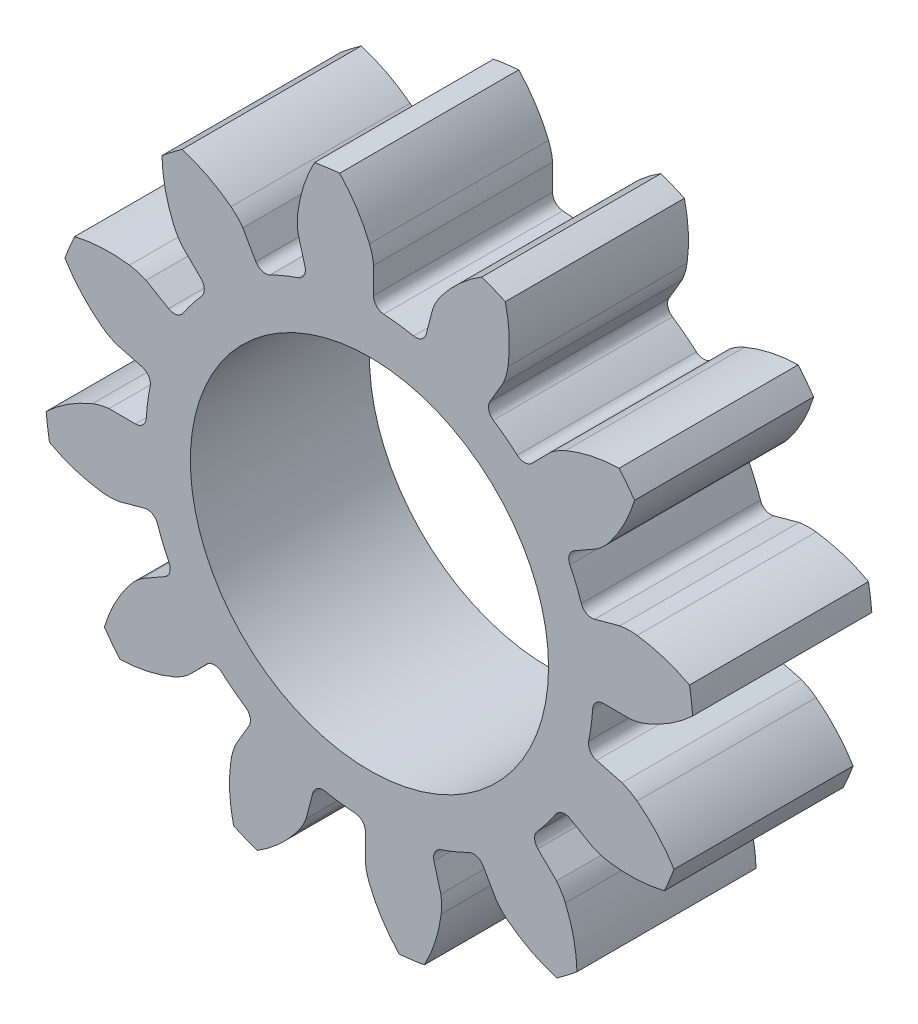
SolidWorks part; units mm, degrees
ref_plane "Front Plane" through (0, 0, 0) normal (0, 0, 1) x (1, 0, 0)
ref_plane "Top Plane" through (0, 0, 0) normal (0, 1, 0) x (1, 0, 0)
ref_plane "Right Plane" through (0, 0, 0) normal (1, 0, 0) x (0, 0, -1)
sketch "Sketch1" plane through (0, 0, 0) normal (0, 0, 1) x (1, 0, 0)
  line L48 (-0.7974, 2.7963) -> (-0.7199, 2.5139)
  line L49 (-1.2685, 2.2867) -> (-1.4135, 2.5411)
  line L50 (-2.0887, 2.023) -> (-1.8804, 1.8171)
  line L51 (-2.2419, 1.346) -> (-2.4946, 1.4939)
  line L52 (-2.8204, 0.7076) -> (-2.5371, 0.6335)
  line L53 (-2.6146, 0.0448) -> (-2.9074, 0.0465)
  line L54 (-2.7963, -0.7974) -> (-2.5139, -0.7199)
  line L55 (-2.2867, -1.2685) -> (-2.5411, -1.4135)
  line L56 (-2.023, -2.0887) -> (-1.8171, -1.8804)
  line L57 (-1.346, -2.2419) -> (-1.4939, -2.4946)
  line L58 (-0.7076, -2.8204) -> (-0.6335, -2.5371)
  line L59 (-0.0448, -2.6146) -> (-0.0465, -2.9074)
  line L60 (0.7974, -2.7963) -> (0.7199, -2.5139)
  line L61 (1.2685, -2.2867) -> (1.4135, -2.5411)
  line L62 (2.0887, -2.023) -> (1.8804, -1.8171)
  line L63 (2.2419, -1.346) -> (2.4946, -1.4939)
  line L64 (2.8204, -0.7076) -> (2.5371, -0.6335)
  line L65 (2.6146, -0.0448) -> (2.9074, -0.0465)
  line L66 (2.7963, 0.7974) -> (2.5139, 0.7199)
  line L67 (2.2867, 1.2685) -> (2.5411, 1.4135)
  line L68 (2.023, 2.0887) -> (1.8171, 1.8804)
  line L69 (1.346, 2.2419) -> (1.4939, 2.4946)
  line L70 (0.7076, 2.8204) -> (0.6335, 2.5371)
  line L71 (0.0448, 2.6146) -> (0.0465, 2.9074)
  circle A0 centre (0, 0) radius 2
  arc A192 (0.0001, 3.0941) -> (-0.3326, 3.6101) centre (-1.5335, 2.4705) ccw
  arc A193 (-0.3326, 3.6101) -> (-0.6131, 3.5732) centre (0, 0) ccw
  arc A194 (-0.6131, 3.5732) -> (-0.8009, 2.9887) centre (0.8418, 2.7833) ccw
  arc A195 (-0.8009, 2.9887) -> (-0.7974, 2.7963) centre (-0.1305, 2.9048) ccw
  arc A196 (-0.7982, 2.3667) -> (-0.7199, 2.5139) centre (-0.8371, 2.4818) ccw
  arc A197 (-0.7982, 2.3667) -> (-1.1091, 2.2379) centre (0, 0) ccw
  arc A198 (-1.2685, 2.2867) -> (-1.1091, 2.2379) centre (-1.163, 2.3468) ccw
  arc A199 (-1.4135, 2.5411) -> (-1.547, 2.6796) centre (-1.9617, 2.1463) ccw
  arc A200 (-1.547, 2.6796) -> (-2.0931, 2.9601) centre (-2.5633, 1.3728) ccw
  arc A201 (-2.0931, 2.9601) -> (-2.3175, 2.7879) centre (0, 0) ccw
  arc A202 (-2.3175, 2.7879) -> (-2.1879, 2.1878) centre (-0.6626, 2.8313) ccw
  arc A203 (-2.1879, 2.1878) -> (-2.0887, 2.023) centre (-1.5655, 2.4504) ccw
  arc A204 (-1.8746, 1.6505) -> (-1.8804, 1.8171) centre (-1.9658, 1.7307) ccw
  arc A205 (-1.8746, 1.6505) -> (-2.0794, 1.3836) centre (0, 0) ccw
  arc A206 (-2.2419, 1.346) -> (-2.0794, 1.3836) centre (-2.1806, 1.4509) ccw
  arc A207 (-2.4946, 1.4939) -> (-2.6795, 1.5472) centre (-2.7721, 0.8779) ccw
  arc A208 (-2.6795, 1.5472) -> (-3.2927, 1.517) centre (-2.9063, -0.0927) ccw
  arc A209 (-3.2927, 1.517) -> (-3.401, 1.2556) centre (0, 0) ccw
  arc A210 (-3.401, 1.2556) -> (-2.9887, 0.8007) centre (-1.9895, 2.1206) ccw
  arc A211 (-2.9887, 0.8007) -> (-2.8204, 0.7076) centre (-2.5809, 1.3394) ccw
  arc A212 (-2.4487, 0.492) -> (-2.5371, 0.6335) centre (-2.5678, 0.516) ccw
  arc A213 (-2.4487, 0.492) -> (-2.4926, 0.1585) centre (0, 0) ccw
  arc A214 (-2.6146, 0.0448) -> (-2.4926, 0.1585) centre (-2.6139, 0.1662) ccw
  arc A215 (-2.9074, 0.0465) -> (-3.0941, 0.0001) centre (-2.8396, -0.6257) ccw
  arc A216 (-3.0941, 0.0001) -> (-3.6101, -0.3326) centre (-2.4705, -1.5335) ccw
  arc A217 (-3.6101, -0.3326) -> (-3.5732, -0.6131) centre (0, 0) ccw
  arc A218 (-3.5732, -0.6131) -> (-2.9887, -0.8009) centre (-2.7833, 0.8418) ccw
  arc A219 (-2.9887, -0.8009) -> (-2.7963, -0.7974) centre (-2.9048, -0.1305) ccw
  arc A220 (-2.3667, -0.7982) -> (-2.5139, -0.7199) centre (-2.4818, -0.8371) ccw
  arc A221 (-2.3667, -0.7982) -> (-2.2379, -1.1091) centre (0, 0) ccw
  arc A222 (-2.2867, -1.2685) -> (-2.2379, -1.1091) centre (-2.3468, -1.163) ccw
  arc A223 (-2.5411, -1.4135) -> (-2.6796, -1.547) centre (-2.1463, -1.9617) ccw
  arc A224 (-2.6796, -1.547) -> (-2.9601, -2.0931) centre (-1.3728, -2.5633) ccw
  arc A225 (-2.9601, -2.0931) -> (-2.7879, -2.3175) centre (0, 0) ccw
  arc A226 (-2.7879, -2.3175) -> (-2.1878, -2.1879) centre (-2.8313, -0.6626) ccw
  arc A227 (-2.1878, -2.1879) -> (-2.023, -2.0887) centre (-2.4504, -1.5655) ccw
  arc A228 (-1.6505, -1.8746) -> (-1.8171, -1.8804) centre (-1.7307, -1.9658) ccw
  arc A229 (-1.6505, -1.8746) -> (-1.3836, -2.0794) centre (0, 0) ccw
  arc A230 (-1.346, -2.2419) -> (-1.3836, -2.0794) centre (-1.4509, -2.1806) ccw
  arc A231 (-1.4939, -2.4946) -> (-1.5472, -2.6795) centre (-0.8779, -2.7721) ccw
  arc A232 (-1.5472, -2.6795) -> (-1.517, -3.2927) centre (0.0927, -2.9063) ccw
  arc A233 (-1.517, -3.2927) -> (-1.2556, -3.401) centre (0, 0) ccw
  arc A234 (-1.2556, -3.401) -> (-0.8007, -2.9887) centre (-2.1206, -1.9895) ccw
  arc A235 (-0.8007, -2.9887) -> (-0.7076, -2.8204) centre (-1.3394, -2.5809) ccw
  arc A236 (-0.492, -2.4487) -> (-0.6335, -2.5371) centre (-0.516, -2.5678) ccw
  arc A237 (-0.492, -2.4487) -> (-0.1585, -2.4926) centre (0, 0) ccw
  arc A238 (-0.0448, -2.6146) -> (-0.1585, -2.4926) centre (-0.1662, -2.6139) ccw
  arc A239 (-0.0465, -2.9074) -> (-0.0001, -3.0941) centre (0.6257, -2.8396) ccw
  arc A240 (-0.0001, -3.0941) -> (0.3326, -3.6101) centre (1.5335, -2.4705) ccw
  arc A241 (0.3326, -3.6101) -> (0.6131, -3.5732) centre (0, 0) ccw
  arc A242 (0.6131, -3.5732) -> (0.8009, -2.9887) centre (-0.8418, -2.7833) ccw
  arc A243 (0.8009, -2.9887) -> (0.7974, -2.7963) centre (0.1305, -2.9048) ccw
  arc A244 (0.7982, -2.3667) -> (0.7199, -2.5139) centre (0.8371, -2.4818) ccw
  arc A245 (0.7982, -2.3667) -> (1.1091, -2.2379) centre (0, 0) ccw
  arc A246 (1.2685, -2.2867) -> (1.1091, -2.2379) centre (1.163, -2.3468) ccw
  arc A247 (1.4135, -2.5411) -> (1.547, -2.6796) centre (1.9617, -2.1463) ccw
  arc A248 (1.547, -2.6796) -> (2.0931, -2.9601) centre (2.5633, -1.3728) ccw
  arc A249 (2.0931, -2.9601) -> (2.3175, -2.7879) centre (0, 0) ccw
  arc A250 (2.3175, -2.7879) -> (2.1879, -2.1878) centre (0.6626, -2.8313) ccw
  arc A251 (2.1879, -2.1878) -> (2.0887, -2.023) centre (1.5655, -2.4504) ccw
  arc A252 (1.8746, -1.6505) -> (1.8804, -1.8171) centre (1.9658, -1.7307) ccw
  arc A253 (1.8746, -1.6505) -> (2.0794, -1.3836) centre (0, 0) ccw
  arc A254 (2.2419, -1.346) -> (2.0794, -1.3836) centre (2.1806, -1.4509) ccw
  arc A255 (2.4946, -1.4939) -> (2.6795, -1.5472) centre (2.7721, -0.8779) ccw
  arc A256 (2.6795, -1.5472) -> (3.2927, -1.517) centre (2.9063, 0.0927) ccw
  arc A257 (3.2927, -1.517) -> (3.401, -1.2556) centre (0, 0) ccw
  arc A258 (3.401, -1.2556) -> (2.9887, -0.8007) centre (1.9895, -2.1206) ccw
  arc A259 (2.9887, -0.8007) -> (2.8204, -0.7076) centre (2.5809, -1.3394) ccw
  arc A260 (2.4487, -0.492) -> (2.5371, -0.6335) centre (2.5678, -0.516) ccw
  arc A261 (2.4487, -0.492) -> (2.4926, -0.1585) centre (0, 0) ccw
  arc A262 (2.6146, -0.0448) -> (2.4926, -0.1585) centre (2.6139, -0.1662) ccw
  arc A263 (2.9074, -0.0465) -> (3.0941, -0.0001) centre (2.8396, 0.6257) ccw
  arc A264 (3.0941, -0.0001) -> (3.6101, 0.3326) centre (2.4705, 1.5335) ccw
  arc A265 (3.6101, 0.3326) -> (3.5732, 0.6131) centre (0, 0) ccw
  arc A266 (3.5732, 0.6131) -> (2.9887, 0.8009) centre (2.7833, -0.8418) ccw
  arc A267 (2.9887, 0.8009) -> (2.7963, 0.7974) centre (2.9048, 0.1305) ccw
  arc A268 (2.3667, 0.7982) -> (2.5139, 0.7199) centre (2.4818, 0.8371) ccw
  arc A269 (2.3667, 0.7982) -> (2.2379, 1.1091) centre (0, 0) ccw
  arc A270 (2.2867, 1.2685) -> (2.2379, 1.1091) centre (2.3468, 1.163) ccw
  arc A271 (2.5411, 1.4135) -> (2.6796, 1.547) centre (2.1463, 1.9617) ccw
  arc A272 (2.6796, 1.547) -> (2.9601, 2.0931) centre (1.3728, 2.5633) ccw
  arc A273 (2.9601, 2.0931) -> (2.7879, 2.3175) centre (0, 0) ccw
  arc A274 (2.7879, 2.3175) -> (2.1878, 2.1879) centre (2.8313, 0.6626) ccw
  arc A275 (2.1878, 2.1879) -> (2.023, 2.0887) centre (2.4504, 1.5655) ccw
  arc A276 (1.6505, 1.8746) -> (1.8171, 1.8804) centre (1.7307, 1.9658) ccw
  arc A277 (1.6505, 1.8746) -> (1.3836, 2.0794) centre (0, 0) ccw
  arc A278 (1.346, 2.2419) -> (1.3836, 2.0794) centre (1.4509, 2.1806) ccw
  arc A279 (1.4939, 2.4946) -> (1.5472, 2.6795) centre (0.8779, 2.7721) ccw
  arc A280 (1.5472, 2.6795) -> (1.517, 3.2927) centre (-0.0927, 2.9063) ccw
  arc A281 (1.517, 3.2927) -> (1.2556, 3.401) centre (0, 0) ccw
  arc A282 (1.2556, 3.401) -> (0.8007, 2.9887) centre (2.1206, 1.9895) ccw
  arc A283 (0.8007, 2.9887) -> (0.7076, 2.8204) centre (1.3394, 2.5809) ccw
  arc A284 (0.492, 2.4487) -> (0.6335, 2.5371) centre (0.516, 2.5678) ccw
  arc A285 (0.492, 2.4487) -> (0.1585, 2.4926) centre (0, 0) ccw
  arc A286 (0.0448, 2.6146) -> (0.1585, 2.4926) centre (0.1662, 2.6139) ccw
  arc A287 (0.0465, 2.9074) -> (0.0001, 3.0941) centre (-0.6257, 2.8396) ccw
  dimension "D1" = 4
extrude "Boss-Extrude1" add sketch "Sketch1" along normal blind 2
